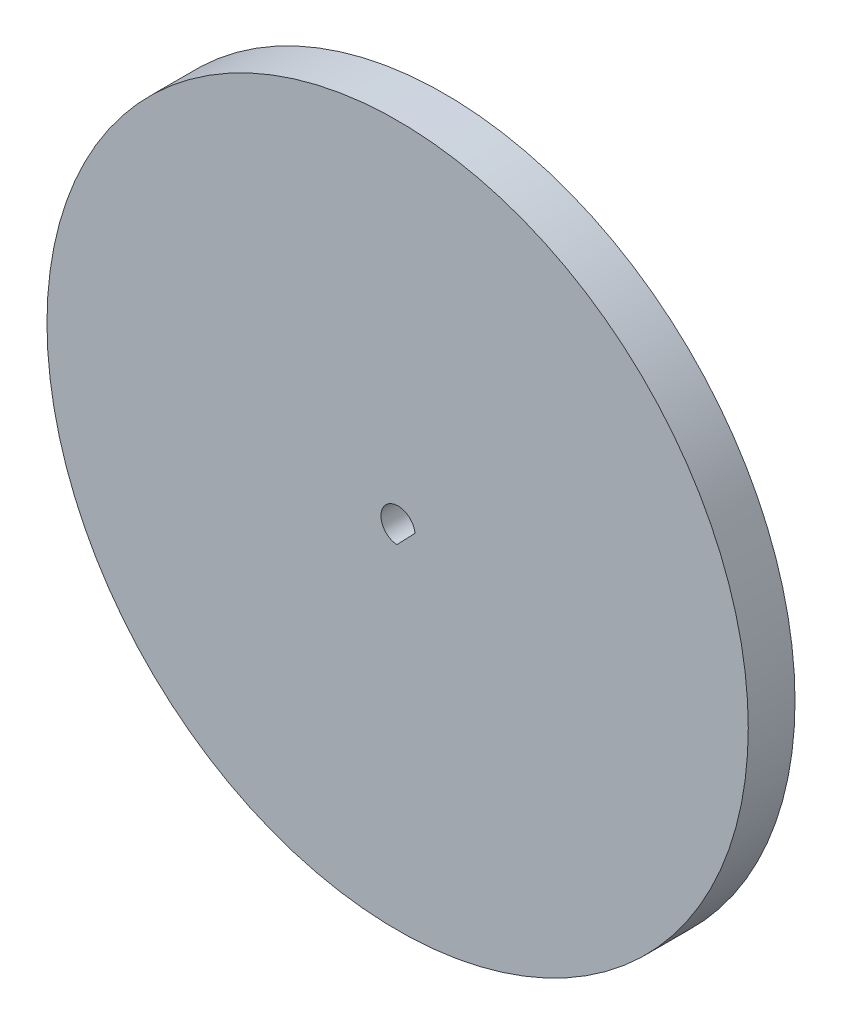
SolidWorks part; units mm, degrees
ref_plane "Front Plane" through (0, 0, 0) normal (0, 0, 1) x (1, 0, 0)
ref_plane "Top Plane" through (0, 0, 0) normal (0, 1, 0) x (1, 0, 0)
ref_plane "Right Plane" through (0, 0, 0) normal (1, 0, 0) x (0, 0, -1)
sketch "Sketch1" plane through (0, 0, 0) normal (0, 0, 1) x (1, 0, 0)
  circle A0 centre (-10.9917, 10.7964) radius 40
  dimension "D1" = 80
extrude "Boss-Extrude1" add sketch "Sketch1" along normal blind 5.334
sketch "Sketch2" plane through (0, 0, 5.334) normal (0, 0, 1) x (1, 0, 0)
  line L0 (-18.7055, 50.0455) -> (-3.1848, -28.4344) construction
  line L1 (-10.9451, 10.8056) -> (-50.2317, 3.036) construction
  line L2 (-11.0767, 8.86) -> (-9.0073, 11.0228)
  circle A0 centre (-10.9451, 10.8056) radius 1.95
  circle A1 centre (-10.9917, 10.7964) radius 40 construction
  dimension "D2" = 3.9
  dimension "D1" = 0
  dimension "D3" = 1.25
extrude "Cut-Extrude1" cut sketch "Sketch2" against normal through all contours L2 A0 region at (-11.0991, 10.9529, 5.334)
equation "\"MDF\"= .21in"
equation "\"Foamcore\"= .13in"
equation "\"Gmaterial\"= \"MDF\""
equation "\"D1@Boss-Extrude1\"=\"MDF\""
